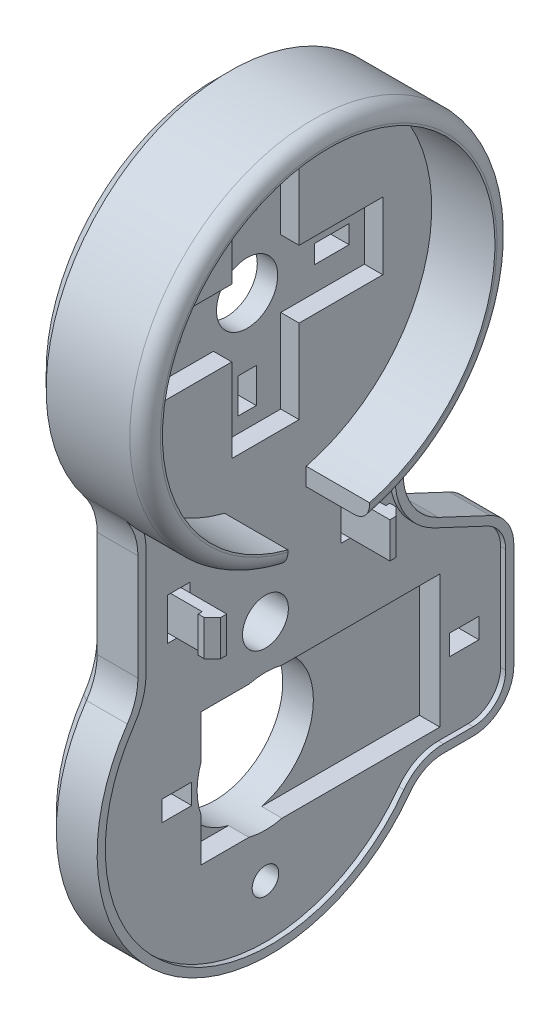
SolidWorks part; units mm, degrees
ref_plane "Front Plane" through (0, 0, 0) normal (0, 0, 1) x (1, 0, 0)
ref_plane "Top Plane" through (0, 0, 0) normal (0, 1, 0) x (1, 0, 0)
ref_plane "Right Plane" through (0, 0, 0) normal (1, 0, 0) x (0, 0, -1)
sketch "Sketch1" plane through (0, 0, 0) normal (1, 0, 0) x (0, 0, -1)
  line L0 (39, 3.3371) -> (39, -7.0385)
  line L1 (68.9482, -28.4) -> (71.85, -28.4)
  line L2 (75.85, -24.4) -> (75.85, -14.1397)
  line L3 (73.5516, -10.5196) -> (68.4476, -8.1205)
  line L4 (65, -2.6905) -> (65, 3.3371)
  arc A0 (66.25, 7.0028) -> (37.75, 7.0028) centre (52, 18) ccw
  arc A1 (37.75, 7.0028) -> (39, 3.3371) centre (33, 3.3371) cw
  arc A2 (39, -7.0385) -> (37.9565, -10.4198) centre (33, -7.0385) cw
  arc A3 (37.9565, -10.4198) -> (65.7199, -30.0381) centre (52, -20) ccw
  arc A4 (65.7199, -30.0381) -> (68.9482, -28.4) centre (68.9482, -32.4) cw
  arc A5 (71.85, -28.4) -> (75.85, -24.4) centre (71.85, -24.4) ccw
  arc A6 (75.85, -14.1397) -> (73.5516, -10.5196) centre (71.85, -14.1397) ccw
  arc A7 (68.4476, -8.1205) -> (65, -2.6905) centre (71, -2.6905) cw
  arc A8 (65, 3.3371) -> (66.25, 7.0028) centre (71, 3.3371) cw
extrude "Boss-Extrude1" add sketch "Sketch1" along normal blind 5.5 from offset 60.6 offset against normal yes
sketch "Sketch2" plane through (0, 0, 0) normal (1, 0, 0) x (0, 0, -1)
  line L0 (39.8, 3.3371) -> (39.8, -7.0385)
  line L1 (68.9482, -27.6) -> (71.85, -27.6)
  line L2 (75.05, -24.4) -> (75.05, -14.1397)
  line L3 (73.2113, -11.2436) -> (68.1073, -8.8446)
  line L4 (64.2, -2.6905) -> (64.2, 3.3371)
  arc A0 (65.6167, 7.4916) -> (38.3833, 7.4916) centre (52, 18) ccw
  arc A1 (38.3833, 7.4916) -> (39.8, 3.3371) centre (33, 3.3371) cw
  arc A2 (39.8, -7.0385) -> (38.6174, -10.8706) centre (33, -7.0385) cw
  arc A3 (38.6174, -10.8706) -> (65.0743, -29.5657) centre (52, -20) ccw
  arc A4 (65.0743, -29.5657) -> (68.9482, -27.6) centre (68.9482, -32.4) cw
  arc A5 (71.85, -27.6) -> (75.05, -24.4) centre (71.85, -24.4) ccw
  arc A6 (75.05, -14.1397) -> (73.2113, -11.2436) centre (71.85, -14.1397) ccw
  arc A7 (68.1073, -8.8446) -> (64.2, -2.6905) centre (71, -2.6905) cw
  arc A8 (64.2, 3.3371) -> (65.6167, 7.4916) centre (71, 3.3371) cw
extrude "Boss-Extrude2" add sketch "Sketch2" along normal blind 0.6 from offset 55.6 separate body offset against normal yes
combine bodies "Combine1" operation type subtract main body 101 bodies to subtract 102
sketch "Sketch3" plane through (0, 0, 0) normal (1, 0, 0) x (0, 0, -1)
  circle A0 centre (52, 18) radius 18
  circle A1 centre (52, 18) radius 16.3
extrude "Boss-Extrude3" add sketch "Sketch3" along normal blind 6.2 from offset 55.6 offset against normal yes
chamfer "Chamfer1" distance 1.5 angle 45 14 edges at (-60.6, -5.9065, -65.9347) (-60.6, 0.3233, -65) (-60.6, -9.3201, -70.9996) (-60.6, 5.2736, -65.3211) (-60.6, -11.9956, -75.2269) (-60.6, 36, -52) (-60.6, -19.2698, -75.85) (-60.6, 5.2736, -38.6789) (-60.6, -27.2284, -74.6784) (-60.6, -1.8507, -39) (-60.6, -28.4, -70.3991) (-60.6, -8.8078, -38.7332) (-60.6, -28.833, -67.1381) (-60.6, -33.8836, -42.1895)
fillet "Fillet1" radius 1.5 1 edges at (-49.4, 18, -70)
sketch "Sketch4" plane through (0, 0, 0) normal (0, 0, 1) x (1, 0, 0)
  line L1 (-57.4, 6.5) -> (-55.1, 6.5)
  line L2 (-57.4, 6.5) -> (-57.4, 29.5)
  line L3 (-57.4, 29.5) -> (-55.1, 29.5)
  line L4 (-55.1, 6.5) -> (-55.1, 29.5)
extrude "Boss-Extrude4" add sketch "Sketch4" along normal blind 6.6 from offset 55.3 separate body offset against normal yes
combine bodies "Combine2" operation type subtract main body 104 bodies to subtract 105
sketch "Sketch5" plane through (0, 0, 0) normal (0, 0, 1) x (1, 0, 0)
  line L1 (-57.4, 14.7) -> (-55.1, 14.7)
  line L2 (-57.4, 14.7) -> (-57.4, 21.3)
  line L3 (-57.4, 21.3) -> (-55.1, 21.3)
  line L4 (-55.1, 14.7) -> (-55.1, 21.3)
extrude "Boss-Extrude5" add sketch "Sketch5" along normal blind 23 from offset 63.5 separate body offset against normal yes
combine bodies "Combine3" operation type subtract main body 106 bodies to subtract 107
sketch "Sketch6" plane through (0, 0, 0) normal (1, 0, 0) x (0, 0, -1)
  circle A0 centre (52, 18) radius 4.6
extrude "Boss-Extrude6" add sketch "Sketch6" along normal blind 2.3 from offset 57.4 separate body offset against normal yes
combine bodies "Combine4" operation type subtract main body 108 bodies to subtract 109
sketch "Sketch7" plane through (0, 0, 0) normal (1, 0, 0) x (0, 0, -1)
  circle A0 centre (52, 18) radius 6.1
extrude "Boss-Extrude7" add sketch "Sketch7" along normal blind 1.7 from offset 61.1 separate body offset against normal yes
combine bodies "Combine5" operation type subtract main body 110 bodies to subtract 111
sketch "Sketch8" plane through (0, 0, 0) normal (1, 0, 0) x (0, 0, -1)
  circle A0 centre (52, 18) radius 3
extrude "Boss-Extrude8" add sketch "Sketch8" along normal blind 2.2 from offset 59.5 separate body offset against normal yes
combine bodies "Combine6" operation type subtract main body 112 bodies to subtract 113
sketch "Sketch9" plane through (0, 0, 0) normal (0, 0, 1) x (1, 0, 0)
  line L1 (-59.6, 24.6) -> (-57.3, 24.6)
  line L2 (-59.6, 24.6) -> (-59.6, 28)
  line L3 (-59.6, 28) -> (-57.3, 28)
  line L4 (-57.3, 24.6) -> (-57.3, 28)
extrude "Boss-Extrude9" add sketch "Sketch9" along normal blind 1.8 from offset 52.9 separate body offset against normal yes
combine bodies "Combine7" operation type subtract main body 114 bodies to subtract 115
sketch "Sketch10" plane through (0, 0, 0) normal (0, 0, 1) x (1, 0, 0)
  line L1 (-59.6, 17.1) -> (-57.3, 17.1)
  line L2 (-59.6, 17.1) -> (-59.6, 18.9)
  line L3 (-59.6, 18.9) -> (-57.3, 18.9)
  line L4 (-57.3, 17.1) -> (-57.3, 18.9)
extrude "Boss-Extrude10" add sketch "Sketch10" along normal blind 3.4 from offset 62 separate body offset against normal yes
combine bodies "Combine8" operation type subtract main body 116 bodies to subtract 117
sketch "Sketch11" plane through (0, 0, 0) normal (0, 0, 1) x (1, 0, 0)
  line L1 (-59.6, 8) -> (-57.3, 8)
  line L2 (-59.6, 8) -> (-59.6, 11.4)
  line L3 (-59.6, 11.4) -> (-57.3, 11.4)
  line L4 (-57.3, 8) -> (-57.3, 11.4)
extrude "Boss-Extrude11" add sketch "Sketch11" along normal blind 1.8 from offset 52.9 separate body offset against normal yes
combine bodies "Combine9" operation type subtract main body 118 bodies to subtract 119
sketch "Sketch12" plane through (0, 0, 0) normal (0, 0, 1) x (1, 0, 0)
  line L1 (-59.6, 17.1) -> (-57.3, 17.1)
  line L2 (-59.6, 17.1) -> (-59.6, 18.9)
  line L3 (-59.6, 18.9) -> (-57.3, 18.9)
  line L4 (-57.3, 17.1) -> (-57.3, 18.9)
extrude "Boss-Extrude12" add sketch "Sketch12" along normal blind 3.4 from offset 45.4 separate body offset against normal yes
combine bodies "Combine10" operation type subtract main body 120 bodies to subtract 121
sketch "Sketch13" plane through (0, 0, 0) normal (0, 0, 1) x (1, 0, 0)
  line L1 (-55.6, -0.6) -> (-49.3, -0.6)
  line L2 (-55.6, -0.6) -> (-55.6, 2.4984)
  line L3 (-55.6, 2.4984) -> (-49.3, 2.4984)
  line L4 (-49.3, -0.6) -> (-49.3, 2.4984)
extrude "Boss-Extrude13" add sketch "Sketch13" along normal blind 8 from offset 56 separate body offset against normal yes
combine bodies "Combine11" operation type subtract main body 122 bodies to subtract 123
sketch "Sketch14" plane through (0, 0, 0) normal (0, 0, 1) x (1, 0, 0)
  line L1 (-59.6, -21) -> (-55.5, -21)
  line L2 (-59.6, -21) -> (-59.6, -19)
  line L3 (-59.6, -19) -> (-55.5, -19)
  line L4 (-55.5, -21) -> (-55.5, -19)
extrude "Boss-Extrude14" add sketch "Sketch14" along normal blind 2.9 from offset 44.775 separate body offset against normal yes
combine bodies "Combine12" operation type subtract main body 124 bodies to subtract 125
sketch "Sketch15" plane through (0, 0, 0) normal (0, 0, 1) x (1, 0, 0)
  line L1 (-59.6, -21) -> (-55.5, -21)
  line L2 (-59.6, -21) -> (-59.6, -19)
  line L3 (-59.6, -19) -> (-55.5, -19)
  line L4 (-55.5, -21) -> (-55.5, -19)
extrude "Boss-Extrude15" add sketch "Sketch15" along normal blind 2.9 from offset 72.925 separate body offset against normal yes
combine bodies "Combine13" operation type subtract main body 126 bodies to subtract 127
sketch "Sketch16" plane through (0, 0, 0) normal (0, 0, 1) x (1, 0, 0)
  line L1 (-57.6, -26.5) -> (-55.5, -26.5)
  line L2 (-57.6, -26.5) -> (-57.6, -13.5)
  line L3 (-57.6, -13.5) -> (-55.5, -13.5)
  line L4 (-55.5, -26.5) -> (-55.5, -13.5)
extrude "Boss-Extrude16" add sketch "Sketch16" along normal blind 23.4 from offset 69.1 separate body offset against normal yes
combine bodies "Combine14" operation type subtract main body 128 bodies to subtract 129
sketch "Sketch17" plane through (0, 0, 0) normal (1, 0, 0) x (0, 0, -1)
  circle A0 centre (52, -20) radius 6.7
extrude "Boss-Extrude17" add sketch "Sketch17" along normal blind 5.6 from offset 61.1 separate body offset against normal yes
combine bodies "Combine15" operation type subtract main body 130 bodies to subtract 131
sketch "Sketch18" plane through (0, 0, 0) normal (1, 0, 0) x (0, 0, -1)
  circle A0 centre (52, -9) radius 2.25
extrude "Boss-Extrude18" add sketch "Sketch18" along normal blind 5.6 from offset 61.1 separate body offset against normal yes
combine bodies "Combine16" operation type subtract main body 132 bodies to subtract 133
sketch "Sketch19" plane through (0, 0, 0) normal (1, 0, 0) x (0, 0, -1)
  circle A0 centre (52, -31) radius 2.3
extrude "Boss-Extrude19" add sketch "Sketch19" along normal blind 1.9 from offset 61.1 separate body offset against normal yes
combine bodies "Combine17" operation type subtract main body 134 bodies to subtract 135
sketch "Sketch20" plane through (0, 0, 0) normal (1, 0, 0) x (0, 0, -1)
  circle A0 centre (52, -31) radius 1.3
extrude "Boss-Extrude20" add sketch "Sketch20" along normal blind 3.75 from offset 59.25 separate body offset against normal yes
combine bodies "Combine18" operation type subtract main body 136 bodies to subtract 137
sketch "Sketch21" plane through (0, 0, 0) normal (0, 0, 1) x (1, 0, 0)
  line L1 (-58.6, -6.05) -> (-55.5, -6.05)
  line L2 (-58.6, -6.05) -> (-58.6, -1.95)
  line L3 (-58.6, -1.95) -> (-55.5, -1.95)
  line L4 (-55.5, -6.05) -> (-55.5, -1.95)
extrude "Boss-Extrude21" add sketch "Sketch21" along normal blind 2.2 from offset 44.6 separate body offset against normal yes
combine bodies "Combine19" operation type subtract main body 138 bodies to subtract 139
sketch "Sketch22" plane through (0, 0, 0) normal (0, 1, 0) x (1, 0, 0)
  line L0 (-58.8, 44) -> (-58.8, 43)
  line L1 (-58.8, 43) -> (-52.8, 43)
  line L2 (-52.8, 43) -> (-52.8, 42.6)
  line L3 (-52.8, 42.6) -> (-52.2, 42.6)
  line L4 (-52.2, 42.6) -> (-51.4, 43.4)
  line L5 (-51.4, 43.4) -> (-51.4, 44)
  line L6 (-51.4, 44) -> (-58.8, 44)
extrude "Boss-Extrude22" add sketch "Sketch22" along normal blind 3.5 from offset 5.75 offset against normal yes
sketch "Sketch23" plane through (0, 0, 0) normal (0, 0, 1) x (1, 0, 0)
  line L1 (-58.6, -6.05) -> (-55.5, -6.05)
  line L2 (-58.6, -6.05) -> (-58.6, -1.95)
  line L3 (-58.6, -1.95) -> (-55.5, -1.95)
  line L4 (-55.5, -6.05) -> (-55.5, -1.95)
extrude "Boss-Extrude23" add sketch "Sketch23" along normal blind 2.2 from offset 61.6 separate body offset against normal yes
combine bodies "Combine20" operation type subtract main body 141 bodies to subtract 142
sketch "Sketch24" plane through (0, 0, 0) normal (0, 1, 0) x (1, 0, 0)
  line L0 (-58.8, 60) -> (-58.8, 61)
  line L1 (-58.8, 61) -> (-52.8, 61)
  line L2 (-52.8, 61) -> (-52.8, 61.4)
  line L3 (-52.8, 61.4) -> (-52.2, 61.4)
  line L4 (-52.2, 61.4) -> (-51.4, 60.6)
  line L5 (-51.4, 60.6) -> (-51.4, 60)
  line L6 (-51.4, 60) -> (-58.8, 60)
extrude "Boss-Extrude24" add sketch "Sketch24" along normal blind 3.5 from offset 5.75 offset against normal yes
